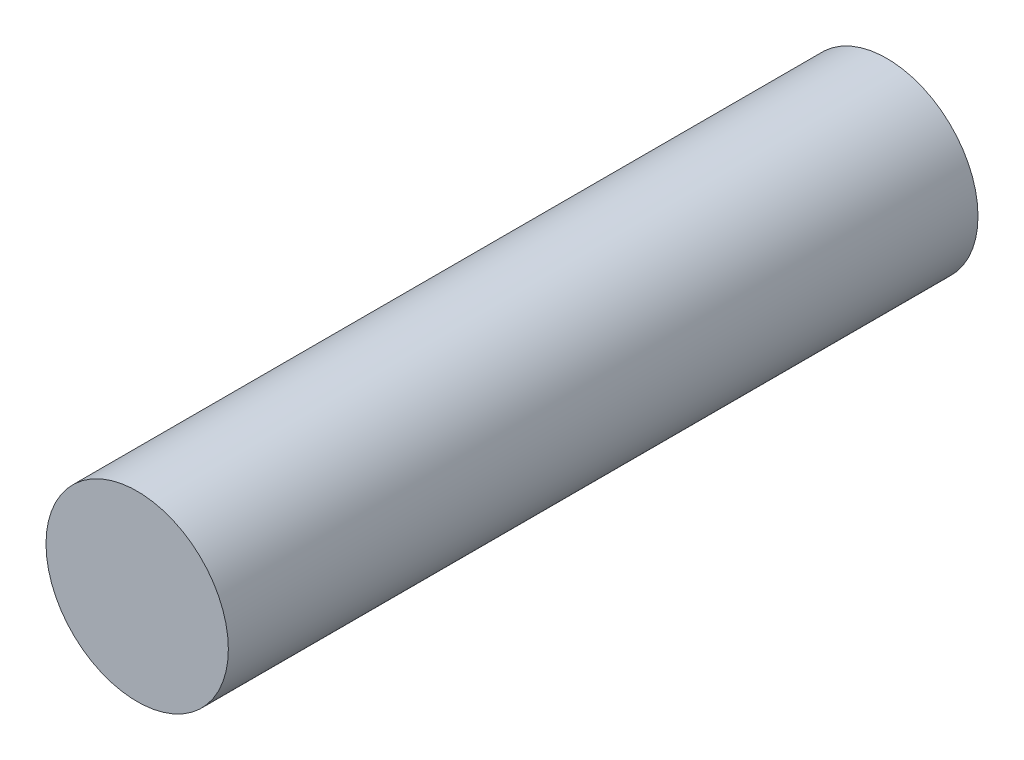
SolidWorks part; units mm, degrees
ref_plane "Front Plane" through (0, 0, 0) normal (0, 0, 1) x (1, 0, 0)
ref_plane "Top Plane" through (0, 0, 0) normal (0, 1, 0) x (1, 0, 0)
ref_plane "Right Plane" through (0, 0, 0) normal (1, 0, 0) x (0, 0, -1)
sketch "Sketch1" plane through (0, 0, 0) normal (0, 0, 1) x (1, 0, 0)
  circle A0 centre (0, 0) radius 2.25
  dimension "D1" = 4.5
extrude "Boss-Extrude1" add sketch "Sketch1" along normal mid plane 18.5
sketch "Sketch2" plane through (0, 0, 0) normal (0, 0, 1) x (1, 0, 0)
  circle A0 centre (0, 0) radius 2.5 construction
  dimension "D1" = 5
